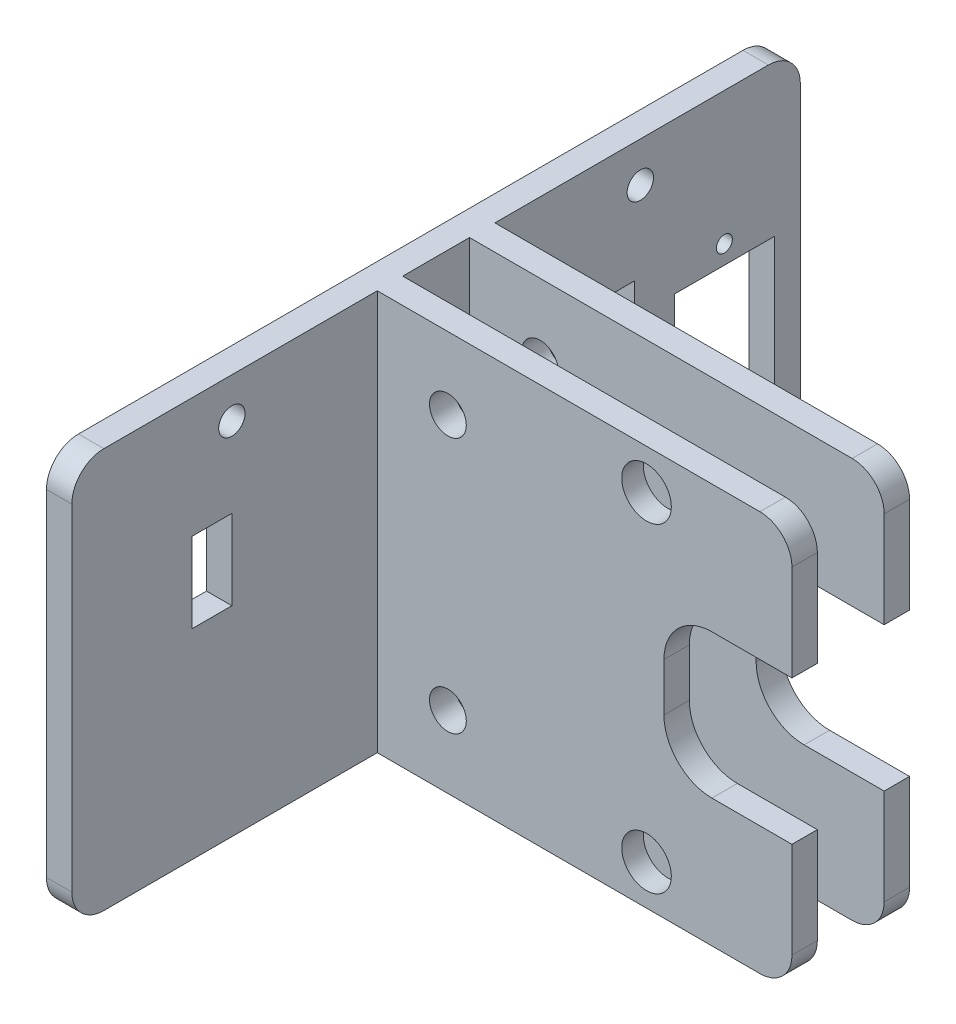
SolidWorks part; units mm, degrees
ref_plane "Front Plane" through (0, 0, 0) normal (0, 0, 1) x (1, 0, 0)
ref_plane "Top Plane" through (0, 0, 0) normal (0, 1, 0) x (1, 0, 0)
ref_plane "Right Plane" through (0, 0, 0) normal (1, 0, 0) x (0, 0, -1)
sketch "Sketch1" plane through (0, 0, 0) normal (0, 1, 0) x (1, 0, 0)
  line L0 (0, 7.35) -> (0, -7.35)
  line L5 (0, -7.35) -> (55, -7.35)
  line L6 (55, -7.35) -> (55, -4.175)
  line L17 (55, -4.175) -> (3.175, -4.175)
  line L18 (3.175, -4.175) -> (3.175, 4.175)
  line L19 (0, 0) -> (39.6882, 0) construction
  line L20 (55, 4.175) -> (3.175, 4.175)
  line L21 (55, 7.35) -> (55, 4.175)
  line L22 (0, 7.35) -> (55, 7.35)
  point P9 (3.175, 0)
  dimension "D1" = 14.7
  dimension "D2" = 3.175
  dimension "D3" = 3.175
  dimension "D4" = 55
extrude "Boss-Extrude1" add sketch "Sketch1" along normal blind 50
sketch "Sketch3" plane through (0, 0, 7.35) normal (0, 0, 1) x (1, 0, 0)
  line L1 (55, 50) -> (55, 0) construction
  line L2 (0, 50) -> (55, 50) construction
  line L3 (55, 25) -> (0, 25) construction
  line L4 (0, 50) -> (0, 0) construction
  circle A0 centre (36.825, 45) radius 3.1
  circle A2 centre (36.825, 5) radius 3.1
  dimension "D1" = 6.2
  dimension "D2" = 5
  dimension "D3" = 18.175
extrude "Cut-Extrude1" cut sketch "Sketch3" against normal blind 2.7
sketch "Sketch4" plane through (0, 0, -7.35) normal (0, 0, -1) x (-1, 0, 0)
  line L1 (-55, 50) -> (-55, 0) construction
  line L2 (0, 50) -> (-55, 50) construction
  line L3 (-55, 25) -> (0, 25) construction
  line L4 (0, 50) -> (0, 0) construction
  circle A0 centre (-36.825, 45) radius 3.1
  circle A2 centre (-36.825, 5) radius 3.1
  dimension "D4" = 6.2
  dimension "D1" = 5
  dimension "D2" = 18.175
extrude "Cut-Extrude2" cut sketch "Sketch4" against normal blind 2.7
fillet "Fillet1" radius 4 4 edges at (55, 50, 5.7625) (55, 50, -5.7625) (55, 0, -5.7625) (55, 0, 5.7625)
sketch "Sketch5" plane through (0, 0, 7.35) normal (0, 0, 1) x (1, 0, 0)
  line L0 (0, 25) -> (55, 25) construction
  line L1 (0, 50) -> (0, 0) construction
  line L2 (55, 46) -> (55, 4) construction
  circle A0 centre (12, 9) radius 2.3
  circle A1 centre (12, 41) radius 2.3
  dimension "D3" = 4.6
  dimension "D1" = 16
  dimension "D2" = 16
  dimension "D4" = 12
extrude "Cut-Extrude3" cut sketch "Sketch5" against normal up to surface (14.7 mm away) up to face at (33.725, 45, -7.35)
sketch "Sketch6" plane through (0, 0, 7.35) normal (0, 0, 1) x (1, 0, 0)
  line L0 (0, 0) -> (51, 0) construction
  line L1 (0, 50) -> (3.175, 50)
  line L2 (0, 50) -> (0, 0)
  line L3 (0, 0) -> (3.175, 0)
  line L4 (3.175, 50) -> (3.175, 0)
  dimension "D1" = 3.175
extrude "Boss-Extrude2" add sketch "Sketch6" along normal blind 38.175
sketch "Sketch7" plane through (0, 0, -7.35) normal (0, 0, -1) x (-1, 0, 0)
  line L0 (-51, 50) -> (0, 50) construction
  line L1 (0, 0) -> (-3.175, 0)
  line L2 (0, 0) -> (0, 50)
  line L3 (0, 50) -> (-3.175, 50)
  line L4 (-3.175, 0) -> (-3.175, 50)
  dimension "D1" = 3.175
extrude "Boss-Extrude3" add sketch "Sketch7" along normal blind 38.175
fillet "Fillet2" radius 4 4 edges at (1.5875, 0, -45.525) (1.5875, 50, -45.525) (1.5875, 0, 45.525) (1.5875, 50, 45.525)
sketch "Sketch10" plane through (0, 0, 0) normal (-1, 0, 0) x (0, 0, 1)
  line L0 (-45.525, 4) -> (-45.525, 46) construction
  line L3 (-41.525, 0) -> (41.525, 0) construction
  line L5 (-29.775, 31.075) -> (-42.275, 31.075)
  line L6 (-29.775, 31.075) -> (-29.775, 8.325)
  line L7 (-29.775, 8.325) -> (-42.275, 8.325)
  line L8 (-42.275, 31.075) -> (-42.275, 8.325)
  circle A0 centre (-36.025, 6) radius 1
  circle A1 centre (-36.025, 33.4) radius 1
  dimension "D1" = 2
  dimension "D2" = 27.4
  dimension "D3" = 9.5
  dimension "D4" = 6
  dimension "D5" = 12.5
  dimension "D6" = 22.75
  dimension "D7" = 2.325
  dimension "D8" = 6.25
extrude "Cut-Extrude7" cut sketch "Sketch10" against normal up to surface (3.175 mm away) up to face at (3.175, 25, -31.7428)
sketch "Sketch11" plane through (0, 0, 0) normal (-1, 0, 0) x (0, 0, 1)
  line L0 (-45.525, 25) -> (45.525, 25) construction
  line L1 (-45.525, 4) -> (-45.525, 46) construction
  line L2 (45.525, 46) -> (45.525, 4) construction
  line L3 (-41.525, 50) -> (41.525, 50) construction
  circle A2 centre (-25.525, 45) radius 1.65
  circle A3 centre (25.525, 45) radius 1.65
  circle A4 centre (-25.525, 5) radius 1.65
  dimension "D3" = 20
  dimension "D1" = 3.3
  dimension "D2" = 5
  dimension "D4" = 20
extrude "Cut-Extrude8" cut sketch "Sketch11" against normal up to surface (3.175 mm away) up to face at (3.175, 6, -35.025)
sketch "Sketch12" plane through (3.175, 0, 0) normal (1, 0, 0) x (0, 0, -1)
  line L0 (-41.525, 0) -> (-7.35, 0) construction
  line L1 (-30.525, 25) -> (-25.525, 25)
  line L2 (-30.525, 25) -> (-30.525, 35)
  line L3 (-30.525, 35) -> (-25.525, 35)
  line L4 (-25.525, 25) -> (-25.525, 35)
  line L5 (-45.525, 4) -> (-45.525, 46) construction
  line L6 (41.525, 0) -> (7.35, 0) construction
  line L7 (19.775, 25) -> (24.775, 25)
  line L8 (19.775, 25) -> (19.775, 35)
  line L9 (19.775, 35) -> (24.775, 35)
  line L10 (24.775, 25) -> (24.775, 35)
  line L11 (29.775, 31.075) -> (29.775, 8.325) construction
  dimension "D1" = 25
  dimension "D2" = 15
  dimension "D3" = 5
  dimension "D4" = 10
  dimension "D5" = 25
  dimension "D6" = 10
  dimension "D7" = 5
  dimension "D8" = 5
extrude "Cut-Extrude9" cut sketch "Sketch12" against normal up to surface (3.175 mm away) up to face at (0, 5, -27.175)
sketch "Sketch13" plane through (0, 0, 7.35) normal (0, 0, 1) x (1, 0, 0)
  line L0 (55, 46) -> (55, 4) construction
  line L1 (45, 16) -> (55, 16)
  line L2 (39, 22) -> (39, 28)
  line L3 (45, 34) -> (55, 34)
  line L4 (55, 16) -> (55, 34)
  line L5 (55, 25) -> (31.9606, 25) construction
  arc A0 (39, 28) -> (45, 34) centre (45, 28) cw
  arc A1 (45, 16) -> (39, 22) centre (45, 22) cw
  point P8 (0, 0)
  point P9 (0, 0)
  point P14 (39, 16)
  dimension "D3" = 6
  dimension "D1" = 18
  dimension "D2" = 16
extrude "Cut-Extrude10" cut sketch "Sketch13" against normal up to surface (14.7 mm away) up to face at (39.925, 5, -7.35)
equation "\"D2@Sketch5\"=\"D1@Sketch5\""
equation "\"D7@Sketch10\"=(\"D2@Sketch10\"-\"D6@Sketch10\")/2"
equation "\"D8@Sketch10\"=\"D5@Sketch10\"/2"
equation "\"D5@Sketch12\"=\"D1@Sketch12\""
equation "\"D6@Sketch12\"=\"D4@Sketch12\""
equation "\"D7@Sketch12\"=\"D3@Sketch12\""
